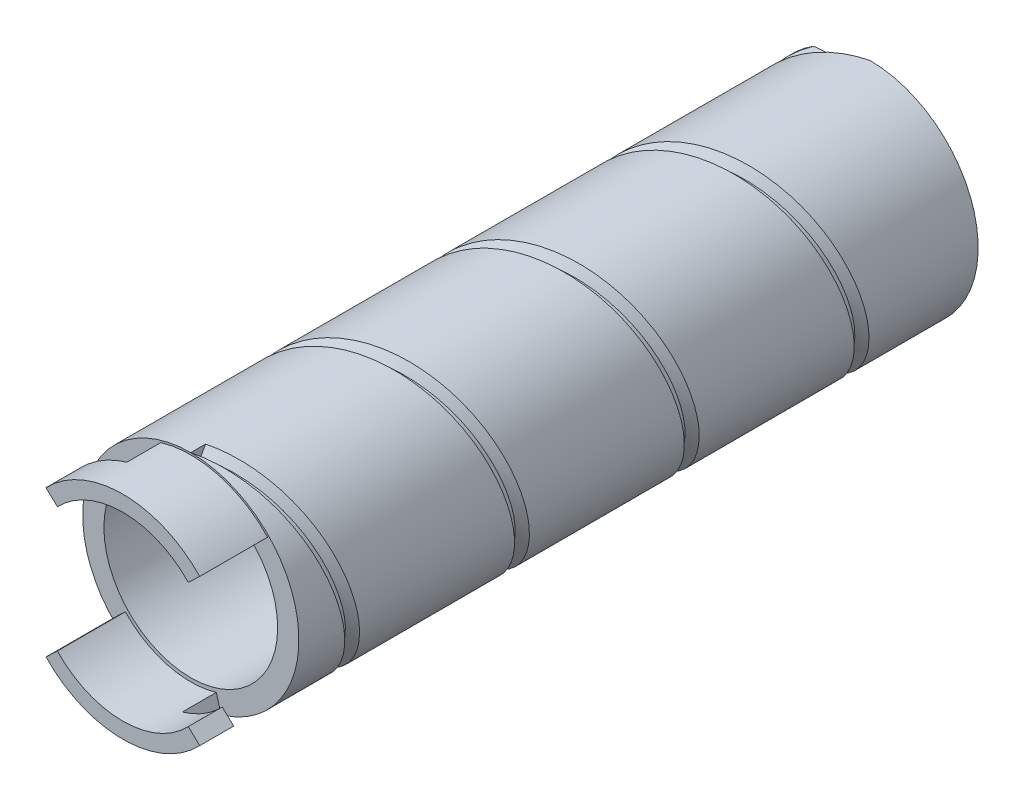
SolidWorks part; units mm, degrees
ref_plane "Front Plane" through (0, 0, 0) normal (1, 0, 0) x (0, 1, 0)
ref_plane "Top Plane" through (0, 0, 0) normal (0, 0, 1) x (0, 1, 0)
ref_plane "Right Plane" through (0, 0, 0) normal (0, 1, 0) x (-1, 0, 0)
sketch "Sketch1" plane through (0, 0, 0) normal (0, 0, 1) x (0, 1, 0)
  circle A0 centre (0, 0) radius 9.55
  circle A1 centre (0, 0) radius 7.6745
extrude "Boss-Extrude1" add sketch "Sketch1" along normal blind 60 contours A0
thread "Thread1" pitch 1.5 start angle 90, offset 0, length 60, pitch 15, diameter 19.1
ref_plane "Plane2" through (0, 9.55, 0) normal (-1, 0, 0) x (0, 1, 0)
sketch "Thread Profile2" plane through (0, 9.55, 0) normal (-1, 0, 0) x (0, 1, 0)
  line L0 (0, 0) -> (0, 1.5) construction
  line L11 (0, 0) -> (0, 1.3125)
  line L12 (0, 1.3125) -> (-0.8119, 0.8437)
  line L13 (-0.8119, 0.8437) -> (-0.8119, 0.4687)
  line L15 (-0.8119, 0.4687) -> (0, 0)
  line L17 (-0.8119, 0.6562) -> (0, 0.6562) construction
  point P2 (0, 0)
  dimension "Pitch" = 1.5
  dimension "Profile_Angle" = 60
  dimension "Profile_Land" = 0.375
  dimension "Profile_Height" = 0.8119
sketch "Sketch8" plane through (0, 0, 60) normal (0, 0, 1) x (1, 0, 0)
sketch "Sketch9" plane through (0, 0, 60) normal (0, 0, 1) x (1, 0, 0)
  line L4 (-6.9106, 6.5914) -> (-5.5534, 5.297)
  line L5 (5.5534, 5.297) -> (6.9106, 6.5914)
  line L6 (55, 0) -> (-55, 0) construction
  line L7 (-6.9106, -6.5914) -> (-5.5534, -5.297)
  line L8 (5.5534, -5.297) -> (6.9106, -6.5914)
  arc A0 (5.5534, -5.297) -> (-5.5534, -5.297) centre (0, 0) cw
  arc A1 (5.5534, 5.297) -> (-5.5534, 5.297) centre (0, 0) ccw
  circle A2 centre (0, 0) radius 7.6745 construction
  arc A3 (6.9106, 6.5914) -> (-6.9106, 6.5914) centre (0, 0) ccw
  circle A4 centre (0, 0) radius 9.55 construction
  arc A5 (6.9106, -6.5914) -> (-6.9106, -6.5914) centre (0, 0) cw
extrude "Boss-Extrude3" add sketch "Sketch9" along normal blind 6
sketch "Sketch10" plane through (0, 0, 0) normal (0.6902, 0.7236, 0) x (-0.7236, 0.6902, 0)
  line L0 (-9.55, 60) -> (-9.55, 63)
  line L1 (-9.55, 66) -> (-9.55, 60) construction
  line L2 (-9.55, 63) -> (-7.6745, 63)
  line L3 (-7.6745, 66) -> (-7.6745, 60) construction
  line L4 (-7.6745, 63) -> (-7.6745, 60)
  line L5 (-7.6745, 60) -> (-9.55, 60)
  line L6 (0, -4.4721) -> (0, 68.3138) construction
revolve "Cut-Revolve1" cut sketch "Sketch10" angle 30 about L6
sketch "Sketch11" plane through (0, 0, 0) normal (-0.6902, -0.7236, 0) x (0.7236, -0.6902, 0)
  line L0 (-9.7092, 60) -> (-9.7092, 63.0078)
  line L1 (-9.7092, 63.0078) -> (-7.6745, 63.0078)
  line L2 (-7.6745, 63.0078) -> (-7.6745, 60)
  line L3 (-7.6745, 60) -> (-9.7092, 60)
  line L5 (-9.55, 60) -> (-7.6745, 60) construction
  line L6 (-7.6745, 66) -> (-7.6745, 60) construction
  line L8 (0, -4.0117) -> (0, 68.2895) construction
revolve "Cut-Revolve2" cut sketch "Sketch11" angle 30 about L8
ref_plane "Plane3" through (-2.689, 9.1636, 60) normal (-0.9595, -0.2816, 0) x (0.2816, -0.9595, 0)
sketch "Sketch13" plane through (0, 0, 66) normal (0, 0, 1) x (1, 0, 0)
  circle A0 centre (0, 0) radius 7.9931
extrude "Cut-Extrude3" cut sketch "Sketch13" against normal blind 6 contours A0
sketch "Sketch15" plane through (0, 0, 0) normal (1, 0, 0) x (0, 1, 0)
  line L0 (0, -4.1104) -> (0, 69.5059)
sketch "Sketch17" plane through (0, 0, 66) normal (0, 0, 1) x (0, -1, 0)
  circle A0 centre (0, 0) radius 9.381
  circle A2 centre (0, 0) radius 9.55
extrude "Cut-Extrude4" cut sketch "Sketch17" against normal blind 6
